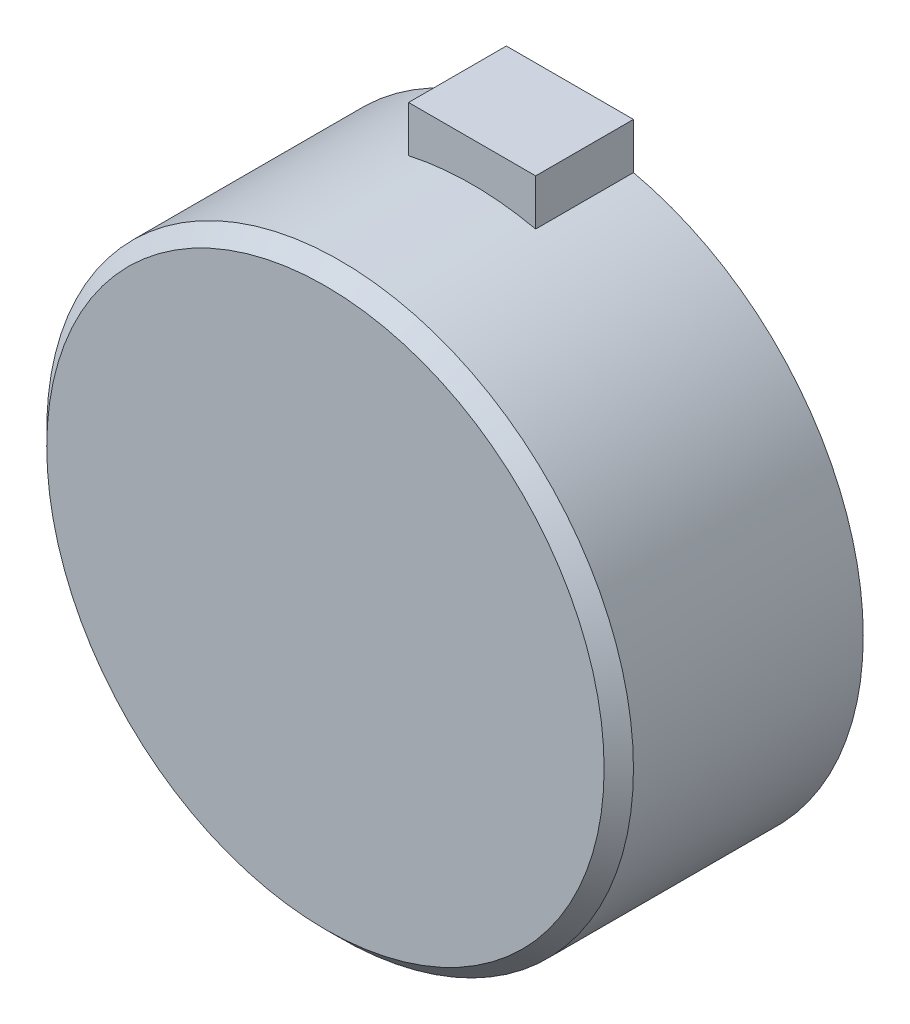
SolidWorks part; units mm, degrees
ref_plane "Front Plane" through (0, 0, 0) normal (0, 0, 1) x (1, 0, 0)
ref_plane "Top Plane" through (0, 0, 0) normal (0, 1, 0) x (1, 0, 0)
ref_plane "Right Plane" through (0, 0, 0) normal (1, 0, 0) x (0, 0, -1)
sketch "SK_Body" plane through (0, 0, 0) normal (0, 1, 0) x (1, 0, 0)
  line L0 (0, -10) -> (0, 60) construction
  line L1 (0, 0) -> (57, 0)
  line L2 (57, 0) -> (60, 3)
  line L3 (60, 3) -> (60, 50)
  line L4 (60, 50) -> (57, 50)
  line L5 (57, 50) -> (0, 50)
  line L6 (0, 50) -> (0, 0)
  dimension "P1" = 10
  dimension "P2" = 60
  dimension "R_front" = 57
  dimension "P4" = 60
  dimension "P5" = 3
  dimension "R_body" = 60
  dimension "L_body" = 50
  dimension "P8" = 57
  dimension "P9" = 50
  dimension "P10" = 50
revolve "Housing_Body" add sketch "SK_Body" angle 360 about L0
ref_plane "PL_Rear" through (0, 0, -50) normal (0, 0, 1) x (1, 0, 0)
sketch "SK_RearHole" plane through (0, 0, -50) normal (0, 0, 1) x (1, 0, 0)
  circle A0 centre (50, 0) radius 2.1
  dimension "D_rh" = 4.2
  dimension "R_rh" = 50
extrude "Rear_Tapped_Hole" cut sketch "SK_RearHole" along normal blind 8
ref_axis "AX_Joint" through (0, 0, -52.5) along (0, 0, 1)
pattern_circular "Rear_Hole_Pattern" count 8 over 360 about axis through (0, 0, -52.5) along (0, 0, 1) of "Rear_Tapped_Hole"
sketch "SK_Connector" plane through (0, 0, -50) normal (0, 0, 1) x (1, 0, 0)
  line L0 (-13, 56) -> (13, 56)
  line L1 (13, 56) -> (13, 68)
  line L2 (13, 68) -> (-13, 68)
  line L3 (-13, 68) -> (-13, 56)
  dimension "P1" = 13
  dimension "P2" = 56
  dimension "P3" = 13
  dimension "P4" = 56
  dimension "P5" = 13
  dimension "P6" = 68
  dimension "P7" = 13
  dimension "P8" = 68
extrude "Connector_Zone" add sketch "SK_Connector" along normal blind 20
equation "\"D_act\" = 120"
equation "\"L_housing\" = 50"
equation "\"PCD_rear\" = 100"
equation "\"D_rear_hole\" = 4.2"
equation "\"D_bearing_boss\" = 74"
equation "\"R_front@SK_Body\" = \"D_act\"/2-3.0"
equation "\"R_body@SK_Body\" = \"D_act\"/2"
equation "\"L_body@SK_Body\" = \"L_housing\""
equation "\"D_rh@SK_RearHole\" = \"D_rear_hole\""
equation "\"R_rh@SK_RearHole\" = \"PCD_rear\"/2"
